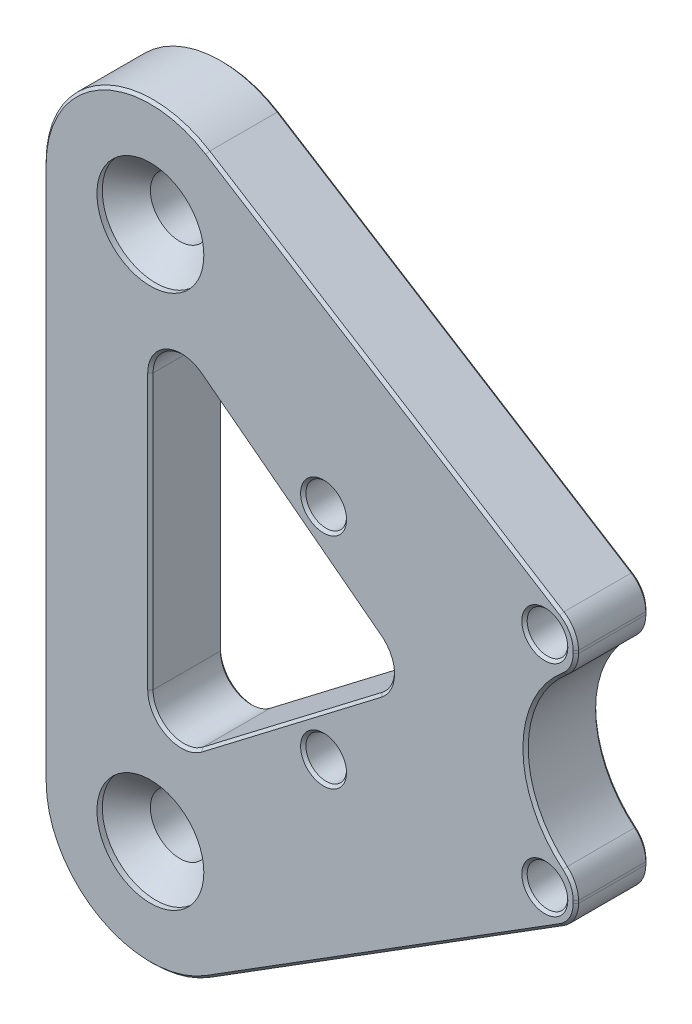
SolidWorks part; units mm, degrees
ref_plane "Front Plane" through (0, 0, 0) normal (0, 0, 1) x (1, 0, 0)
ref_plane "Top Plane" through (0, 0, 0) normal (0, 1, 0) x (1, 0, 0)
ref_plane "Right Plane" through (0, 0, 0) normal (1, 0, 0) x (0, 0, -1)
sketch "Sketch1" plane through (0, 0, 1.1) normal (0, 0, 1) x (1, 0, 0)
  line L0 (-27.3895, 33.4731) -> (5.7397, 12.7072)
  line L1 (-22.7005, 26.5365) -> (-22.7005, -11.673) construction
  line L2 (-27.3895, -33.4731) -> (5.7397, -12.7072)
  line L3 (7.0995, 10.25) -> (7.0995, 8.5352)
  line L4 (-42.7005, 13.15) -> (-42.7005, -8.8269) construction
  line L5 (-22.7005, 0) -> (-42.7005, 0) construction
  line L6 (-32.7005, 21.0577) -> (-32.7005, -15.7288) construction
  line L7 (-30.8798, 0) -> (28.9169, 0) construction
  line L8 (-42.7005, 25) -> (-42.7005, -25)
  line L9 (7.0995, -8.5352) -> (7.0995, -10.25)
  circle A0 centre (-16.5005, -10.25) radius 1.25
  circle A1 centre (4.1995, 10.25) radius 1.25
  circle A2 centre (4.1995, -10.25) radius 1.25
  circle A4 centre (-16.5005, 10.25) radius 1.25
  circle A5 centre (-16.5005, -10.25) radius 2.9 construction
  arc A6 (5.7397, -12.7072) -> (7.0995, -10.25) centre (4.1995, -10.25) ccw
  circle A7 centre (-16.5005, 10.25) radius 2.9 construction
  arc A8 (7.0995, 10.25) -> (5.7397, 12.7072) centre (4.1995, 10.25) ccw
  circle A9 centre (-32.7005, 25) radius 2.75
  arc A10 (-27.3895, 33.4731) -> (-42.7005, 25) centre (-32.7005, 25) ccw
  circle A12 centre (12.4995, 0) radius 10.1
  circle A13 centre (12.4995, 0) radius 10.1
  circle A15 centre (-32.7005, -25) radius 2.75
  arc A16 (-27.3895, -33.4731) -> (-42.7005, -25) centre (-32.7005, -25) cw
  point P31 (-32.7005, 0)
  arc M22 (2.5211, -6.75) -> (2.5211, 6.75) centre (12.4995, 0) cw
  line M23 (2.5211, 6.75) -> (-21.1722, 6.75)
  line M24 (-21.1722, 6.75) -> (-21.1722, -6.75)
  line M25 (-21.1722, -6.75) -> (2.5211, -6.75)
  line M26 (-2.5005, -5.5) -> (-17.5005, -5.5)
  arc M27 (-17.5005, -5.5) -> (-18.0005, -5) centre (-17.5005, -5) cw
  line M28 (-18.0005, -5) -> (-18.0005, 5)
  arc M29 (-18.0005, 5) -> (-17.5005, 5.5) centre (-17.5005, 5) cw
  line M30 (-17.5005, 5.5) -> (-2.5005, 5.5)
  arc M31 (-2.5005, 5.5) -> (-2.0005, 5) centre (-2.5005, 5) cw
  line M32 (-2.0005, 5) -> (-2.0005, -5)
  arc M33 (-2.0005, -5) -> (-2.5005, -5.5) centre (-2.5005, -5) cw
  dimension "D1" = 2.5
  dimension "D2" = 5.8
  dimension "D7" = 50
  dimension "D6" = 5.5
  dimension "D3" = 35.2
  dimension "D4" = 0.5
  dimension "D5" = 20
extrude "Boss-Extrude1" add sketch "Sketch1" along normal blind 6.8 contours L7 A13 L3 A8 A7 M24 M23 M22 | L7 M24 M28 M29 M30 M31 M32 M22 M23 | L7 M28 M32 M31 M30 M29 | L7 M24 | L7 M24 M25 M22 M32 M33 M26 M27 M28 | L7 M28 M27 M26 M33 M32 | L7 A5 A6 L3 A13 M22 M25 | A6 A5 | A5 A0 | A6 A2 | A8 A1 | A7 A4 region at (-23.793, 0, 1.1) region at (-9.3255, -6.4773, 1.1) region at (-10.0005, 0, 1.1)
sketch "Sketch2" plane through (0, 0, 7.9) normal (0, 0, 1) x (1, 0, 0)
  circle A0 centre (-16.5005, 10.25) radius 1.9
  circle A1 centre (4.1995, 10.25) radius 1.9
  circle A2 centre (-16.5005, -10.25) radius 1.9
  circle A3 centre (4.1995, -10.25) radius 1.9
  dimension "D1" = 3.8
extrude "Cut-Extrude1" cut sketch "Sketch2" against normal offset from surface (5.3 mm away) 1.5 up to face at (-10.9363, 0, 1.1)
fillet "Fillet1" radius 2.9 2 edges at (7.0995, -8.5352, 4.5) (7.0995, 8.5352, 4.5)
hole_wizard "CSK for M5 Flat Head Machine Screw1" positions "Sketch3" profile "Sketch4" countersink size "M5" standard "ANSI Metric" end condition through all
sketch "Sketch3" plane through (0, 0, 7.9) normal (0, 0, 1) x (1, 0, 0)
  point P0 (-32.7005, 25)
  point P3 (-32.7005, -25)
sketch "Sketch4" plane through (-32.7005, 25, 7.9) normal (1, 0, 0) x (0, -1, 0)
  line L0 (0, 0) -> (0, 6.8)
  line L1 (0, 6.8) -> (2.75, 6.8)
  line L2 (2.75, 6.8) -> (2.75, 2.75)
  line L3 (2.75, 2.75) -> (5, 0.5)
  line L4 (5, 0.5) -> (5, 0)
  line L6 (5, 0) -> (0, 0)
  line L7 (-2.75, 2.75) -> (-5, 0.5) construction
  line L11 (0, -6.35) -> (0, 107.95) construction
  dimension "Thru Hole Dia." = 5.5
  dimension "Thru Hole Depth" = 6.8
  dimension "C'Sink Dia." = 10
  dimension "C'Sink Angle" = 90
  dimension "Head Clearance" = 0.5
sketch "Sketch5" plane through (0, 0, 7.9) normal (0, 0, 1) x (1, 0, 0)
  line L0 (-32.7005, 25) -> (-32.7005, -25)
  line L1 (-32.7005, -25) -> (0, 0) construction
  line L2 (0, 0) -> (-32.7005, 25) construction
  line L3 (-3.0368, -3.9722) -> (-35.7373, 21.0278)
  line L4 (-58.5824, 0) -> (16.7402, 0) construction
  line L5 (-3.0368, 3.9722) -> (-35.7373, -21.0278)
  dimension "D1" = 5
extrude "Cut-Extrude2" cut sketch "Sketch5" against normal up to next contours L5 L3 L0 region at (-24.5445, 0, 7.9)
fillet "Fillet2" radius 2.9 3 edges at (-32.7005, -18.7062, 4.5) (-8.2324, 0, 4.5) (-32.7005, 18.7062, 4.5)
chamfer "Chamfer1" distance 0.25 angle 45 50 edges at (-14.6005, -10.25, 7.9) (-14.6005, -10.25, 2.6) (6.0995, -10.25, 7.9) (6.0995, -10.25, 2.6) (6.0995, 10.25, 7.9) (6.0995, 10.25, 2.6) (-14.6005, 10.25, 7.9) (-14.6005, 10.25, 2.6) (-15.2505, -10.25, 1.1) (5.4495, -10.25, 1.1) (5.4495, 10.25, 1.1) (-15.2505, 10.25, 1.1) (-29.9505, 25, 1.1) (-29.9505, -25, 1.1) (7.0995, 10.1277, 1.1) (6.7369, 11.6542, 1.1) (6.8243, 8.7725, 1.1) (-10.8249, 23.0901, 1.1) (2.3995, 0, 1.1) (-37.5425, 33.7496, 1.1) (6.8243, -8.7725, 1.1) (-42.7005, 0, 1.1) (7.0995, -10.1277, 1.1) (-37.5425, -33.7496, 1.1) (6.7369, -11.6542, 1.1) (-10.8249, -23.0901, 1.1) (-10.1072, 0, 7.9) (-19.6425, 8.7232, 7.9) (-19.6425, -8.7232, 7.9) (-31.0854, 15.4385, 7.9) (-31.0854, -15.4385, 7.9) (-32.7005, 0, 7.9) (2.3995, 0, 7.9) (6.8243, 8.7725, 7.9) (6.8243, -8.7725, 7.9) (7.0995, 10.1277, 7.9) (7.0995, -10.1277, 7.9) (6.7369, 11.6542, 7.9) (6.7369, -11.6542, 7.9) (-10.8249, 23.0901, 7.9) (-10.8249, -23.0901, 7.9) (-37.5425, 33.7496, 7.9) (-37.5425, -33.7496, 7.9) (-42.7005, 0, 7.9) (-10.1072, 0, 1.1) (-19.6425, -8.7232, 1.1) (-19.6425, 8.7232, 1.1) (-31.0854, -15.4385, 1.1) (-31.0854, 15.4385, 1.1) (-32.7005, 0, 1.1)
